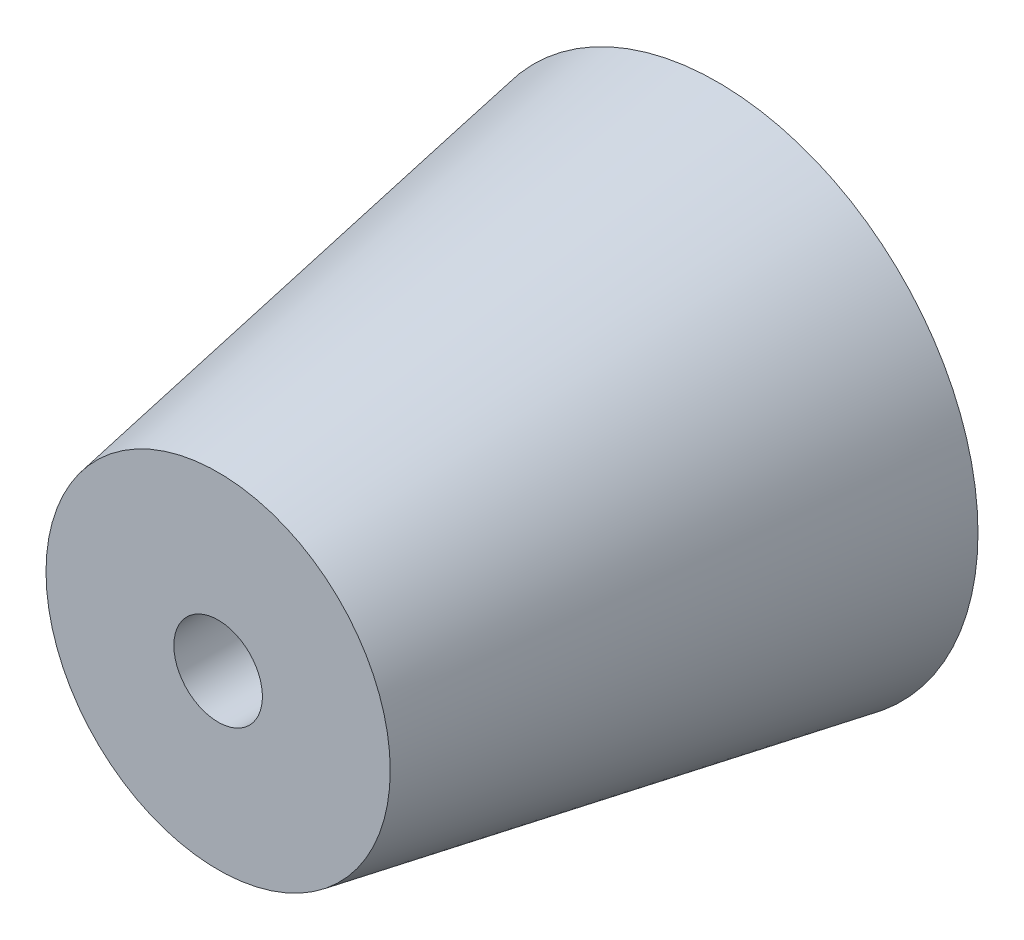
SolidWorks part; units mm, degrees
material "ABS"
ref_plane "Front Plane" through (0, 0, 0) normal (0, 0, 1) x (1, 0, 0)
ref_plane "Top Plane" through (0, 0, 0) normal (0, 1, 0) x (1, 0, 0)
ref_plane "Right Plane" through (0, 0, 0) normal (1, 0, 0) x (0, 0, -1)
sketch "Sketch1" plane through (0, 0, 0) normal (0, 0, 1) x (1, 0, 0)
  circle A0 centre (0, 0) radius 17.5
  dimension "D1" = 35
extrude "Boss-Extrude" add sketch "Sketch1" along normal blind 50.8
draft "Draft3" type of draft neutral plane draft angle 10 faces to draft 1 face at (17.5, 0, 50.8) neutral plane through (0, 0, 50.8) neutral plane normal (0, 0, 1) parameters "D1"=10
sketch "Sketch2" plane through (0, 0, 0) normal (0, 0, -1) x (-1, 0, 0)
  circle A0 centre (0, 0) radius 4.5
  dimension "D1" = 9
extrude "Cut-Extrude1" cut sketch "Sketch2" against normal through all
sketch "Sketch3" plane through (0, 0, 0) normal (0, 0, -1) x (-1, 0, 0)
  circle A0 centre (0, 0) radius 11.5
extrude "Cut-Extrude3" cut sketch "Sketch3" against normal blind 8
